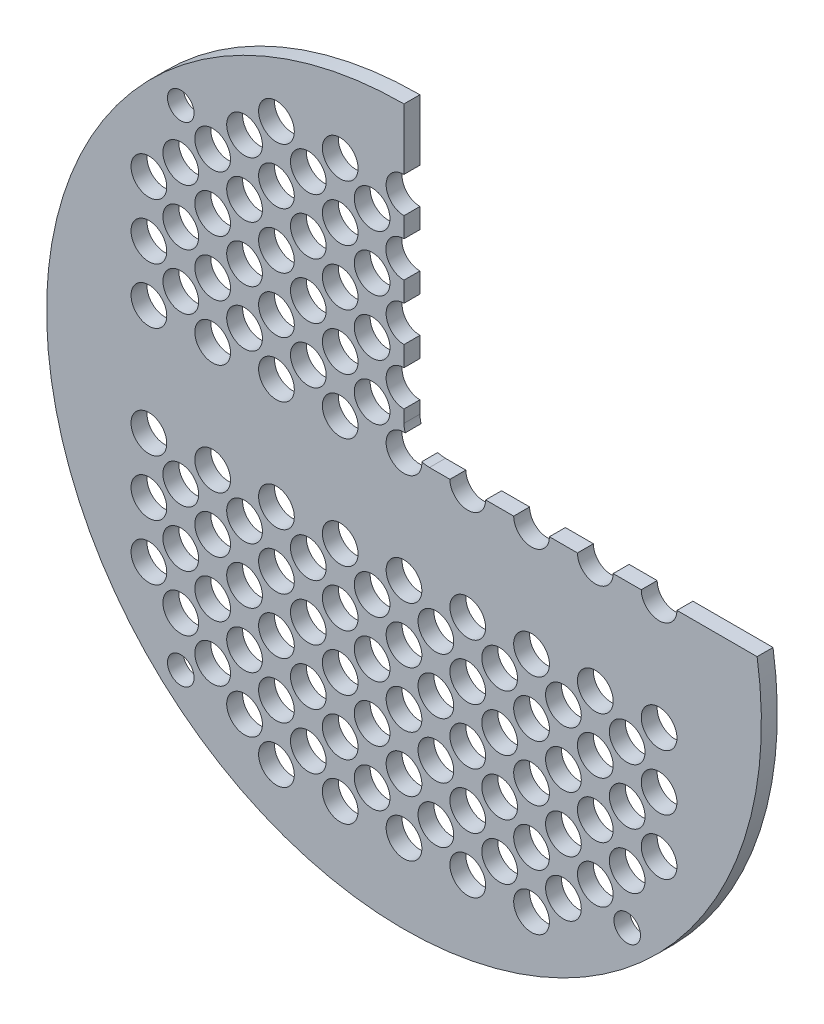
SolidWorks part; units mm, degrees
material "ASTM A105"
ref_plane "Front Plane" through (0, 0, 0) normal (0, 0, 1) x (1, 0, 0)
ref_plane "Top Plane" through (0, 0, 0) normal (0, 1, 0) x (1, 0, 0)
ref_plane "Right Plane" through (0, 0, 0) normal (1, 0, 0) x (0, 0, -1)
ref_axis "Axis1" through (0, 0, -1.27) along (0, 0, 1)
ref_plane "Hub End Plane" through (0, 0, 88.9) normal (0, 0, 1) x (1, 0, 0)
sketch "Sketch1" plane through (0, 0, 0) normal (0, 0, 1) x (1, 0, 0)
  circle A1 centre (0, 0) radius 213.5188
  dimension "D1" = 427.0375
extrude "Boss-Extrude1" add sketch "Sketch1" along normal blind 9.525
sketch "Sketch11" plane through (0, 0, 0) normal (0, 0, 1) x (1, 0, 0)
  line L0 (-313.3441, 0) -> (312.1404, 0) construction
  line L1 (0, 318.8395) -> (0, 177.038) construction
  line L5 (15.24, 33.02) -> (27.432, 33.02)
  line L6 (216.2099, 230.0551) -> (216.2099, 33.02)
  line L18 (0, 230.0551) -> (216.2099, 230.0551)
  line L21 (48.768, 33.02) -> (65.532, 33.02)
  line L22 (86.868, 33.02) -> (103.632, 33.02)
  line L23 (124.968, 33.02) -> (141.732, 33.02)
  line L24 (163.068, 33.02) -> (216.2099, 33.02)
  line L25 (0, 89.027) -> (0, 77.0255)
  line L26 (0, 89.027) -> (0, 77.0255) construction
  line L27 (0, 55.6895) -> (0, 48.26)
  line L28 (0, 55.6895) -> (0, -223.744) construction
  line L31 (0, 110.363) -> (0, 122.3531)
  line L32 (0, 155.702) -> (0, 143.7005) construction
  line L33 (0, 177.038) -> (0, 230.0551)
  line L34 (0, 143.7005) -> (0, 155.702)
  line L35 (0, 122.3531) -> (0, 110.363) construction
  circle A20 centre (-38.1, 33.02) radius 10.668
  circle A21 centre (-76.2, 33.02) radius 10.668
  circle A22 centre (-114.3, 33.02) radius 10.668
  circle A23 centre (-152.4, 33.02) radius 10.668
  circle A95 centre (-38.1, 66.3575) radius 10.668
  circle A98 centre (-76.2, 66.3575) radius 10.668
  circle A146 centre (-114.3, 66.3575) radius 10.668
  circle A150 centre (-152.4, 66.3575) radius 10.668
  circle A161 centre (-38.1, 99.695) radius 10.668
  circle A163 centre (-76.2, 99.695) radius 10.668
  circle A164 centre (-114.3, 99.695) radius 10.668
  circle A166 centre (-133.35, 146.05) radius 7.9375
  circle A172 centre (-152.4, 99.695) radius 10.668
  circle A180 centre (-38.1, 133.0325) radius 10.668
  circle A181 centre (-76.2, 133.0325) radius 10.668
  circle A182 centre (-114.3, 133.0325) radius 10.668
  arc A185 (0, 177.038) -> (0, 155.702) centre (0, 166.37) ccw
  circle A191 centre (-38.1, 166.37) radius 10.668
  circle A192 centre (-76.2, 166.37) radius 10.668
  circle A208 centre (-19.05, 49.8475) radius 10.668
  circle A209 centre (-57.15, 49.8475) radius 10.668
  circle A210 centre (-95.25, 49.8475) radius 10.668
  circle A211 centre (-133.35, 49.8475) radius 10.668
  circle A218 centre (-19.05, 83.185) radius 10.668
  circle A219 centre (-57.15, 83.185) radius 10.668
  circle A220 centre (-95.25, 83.185) radius 10.668
  circle A221 centre (-133.35, 83.185) radius 10.668
  circle A228 centre (-19.05, 116.5225) radius 10.668
  circle A229 centre (-57.15, 116.5225) radius 10.668
  circle A230 centre (-95.25, 116.5225) radius 10.668
  circle A231 centre (-133.35, 116.5225) radius 10.668
  circle A238 centre (-19.05, 149.86) radius 10.668
  circle A239 centre (-57.15, 149.86) radius 10.668
  circle A240 centre (-95.25, 149.86) radius 10.668
  circle A257 centre (-133.35, -146.05) radius 7.9375
  circle A258 centre (133.35, -146.05) radius 7.9375
  arc A260 (0, 48.26) -> (0.7094, 43.6644) centre (15.24, 48.26) ccw
  circle A267 centre (-152.4, 199.7075) radius 10.668 [skipped]
  circle A268 centre (-114.3, 199.7075) radius 10.668 [skipped]
  circle A271 centre (-152.4, 166.37) radius 10.668 [skipped]
  circle A274 centre (114.3, -133.0325) radius 10.668
  arc A275 (163.068, 33.02) -> (141.732, 33.02) centre (152.4, 33.02) cw
  arc A276 (124.968, 33.02) -> (103.632, 33.02) centre (114.3, 33.02) cw
  arc A277 (86.868, 33.02) -> (65.532, 33.02) centre (76.2, 33.02) cw
  arc A278 (48.768, 33.02) -> (27.432, 33.02) centre (38.1, 33.02) cw
  circle A280 centre (152.4, -33.02) radius 10.668
  circle A281 centre (-114.3, 166.37) radius 10.668 [skipped]
  circle A283 centre (-76.2, 199.7075) radius 10.668 [skipped]
  circle A284 centre (-152.4, 133.0325) radius 10.668 [skipped]
  arc A285 (0, 110.363) -> (0, 89.027) centre (0, 99.695) ccw
  arc A286 (0, 143.7005) -> (0, 122.3531) centre (-0.1716, 133.0268) ccw
  arc A287 (0.7094, 43.6644) -> (10.6444, 33.7294) centre (0, 33.02) ccw
  arc A288 (0, 77.0255) -> (0, 55.6895) centre (0, 66.3575) ccw
  arc A290 (10.6444, 33.7294) -> (15.24, 33.02) centre (15.24, 48.26) ccw
  circle A293 centre (-38.1, 199.7075) radius 10.668 [skipped]
  circle A303 centre (95.25, -149.86) radius 10.668
  circle A304 centre (57.15, -149.86) radius 10.668
  circle A305 centre (-95.25, -149.86) radius 10.668
  circle A306 centre (-57.15, -149.86) radius 10.668
  circle A307 centre (-19.05, -149.86) radius 10.668
  circle A308 centre (19.05, -149.86) radius 10.668
  circle A309 centre (133.35, -116.5225) radius 10.668
  circle A310 centre (95.25, -116.5225) radius 10.668
  circle A311 centre (57.15, -116.5225) radius 10.668
  circle A316 centre (19.05, -116.5225) radius 10.668
  circle A318 centre (133.35, -83.185) radius 10.668
  circle A319 centre (95.25, -83.185) radius 10.668
  circle A320 centre (57.15, -83.185) radius 10.668
  circle A326 centre (19.05, -83.185) radius 10.668
  circle A328 centre (133.35, -49.8475) radius 10.668
  circle A329 centre (95.25, -49.8475) radius 10.668
  circle A330 centre (57.15, -49.8475) radius 10.668
  circle A336 centre (19.05, -49.8475) radius 10.668
  circle A337 centre (-76.2, -166.37) radius 10.668
  circle A338 centre (-38.1, -166.37) radius 10.668
  circle A339 centre (76.2, -166.37) radius 10.668
  circle A340 centre (38.1, -166.37) radius 10.668
  circle A341 centre (0, -166.37) radius 10.668
  circle A346 centre (76.2, -133.0325) radius 10.668
  circle A347 centre (38.1, -133.0325) radius 10.668
  circle A353 centre (152.4, -99.695) radius 10.668
  circle A354 centre (114.3, -99.695) radius 10.668
  circle A355 centre (76.2, -99.695) radius 10.668
  circle A356 centre (38.1, -99.695) radius 10.668
  circle A362 centre (152.4, -66.3575) radius 10.668
  circle A363 centre (114.3, -66.3575) radius 10.668
  circle A364 centre (76.2, -66.3575) radius 10.668
  circle A365 centre (38.1, -66.3575) radius 10.668
  circle A372 centre (114.3, -33.02) radius 10.668
  circle A373 centre (76.2, -33.02) radius 10.668
  circle A374 centre (38.1, -33.02) radius 10.668
  circle A378 centre (0, -133.0325) radius 10.668
  circle A379 centre (0, -99.695) radius 10.668
  circle A380 centre (0, -66.3575) radius 10.668
  circle A381 centre (0, -33.02) radius 10.668
  circle A382 centre (-38.1, -33.02) radius 10.668
  circle A383 centre (-76.2, -33.02) radius 10.668
  circle A384 centre (-114.3, -33.02) radius 10.668
  circle A385 centre (-38.1, -66.3575) radius 10.668
  circle A386 centre (-76.2, -66.3575) radius 10.668
  circle A387 centre (-114.3, -66.3575) radius 10.668
  circle A388 centre (-152.4, -66.3575) radius 10.668
  circle A389 centre (-38.1, -99.695) radius 10.668
  circle A390 centre (-76.2, -99.695) radius 10.668
  circle A391 centre (-114.3, -99.695) radius 10.668
  circle A392 centre (-152.4, -99.695) radius 10.668
  circle A393 centre (-38.1, -133.0325) radius 10.668
  circle A394 centre (-76.2, -133.0325) radius 10.668
  circle A395 centre (-38.1, -166.37) radius 10.668
  circle A396 centre (-76.2, -166.37) radius 10.668
  circle A397 centre (-19.05, -49.8475) radius 10.668
  circle A398 centre (-57.15, -49.8475) radius 10.668
  circle A399 centre (-95.25, -49.8475) radius 10.668
  circle A400 centre (-133.35, -49.8475) radius 10.668
  circle A401 centre (-19.05, -83.185) radius 10.668
  circle A402 centre (-57.15, -83.185) radius 10.668
  circle A403 centre (-95.25, -83.185) radius 10.668
  circle A404 centre (-133.35, -83.185) radius 10.668
  circle A405 centre (-19.05, -116.5225) radius 10.668
  circle A406 centre (-57.15, -116.5225) radius 10.668
  circle A407 centre (-95.25, -116.5225) radius 10.668
  circle A408 centre (-133.35, -116.5225) radius 10.668
  circle A409 centre (-19.05, -149.86) radius 10.668
  circle A410 centre (-57.15, -149.86) radius 10.668
  circle A411 centre (-95.25, -149.86) radius 10.668
  circle A412 centre (-152.4, -33.02) radius 10.668
  circle A413 centre (-114.3, -133.0325) radius 10.668
  circle A414 centre (-133.35, -146.05) radius 7.9375
  point P17 (0, 133.0325)
  point P21 (0, 33.02)
  point P32 (0, 122.3531)
  dimension "D10" = 6
extrude "Cut-Extrude4" cut sketch "Sketch11" against normal through all and the other way through all
